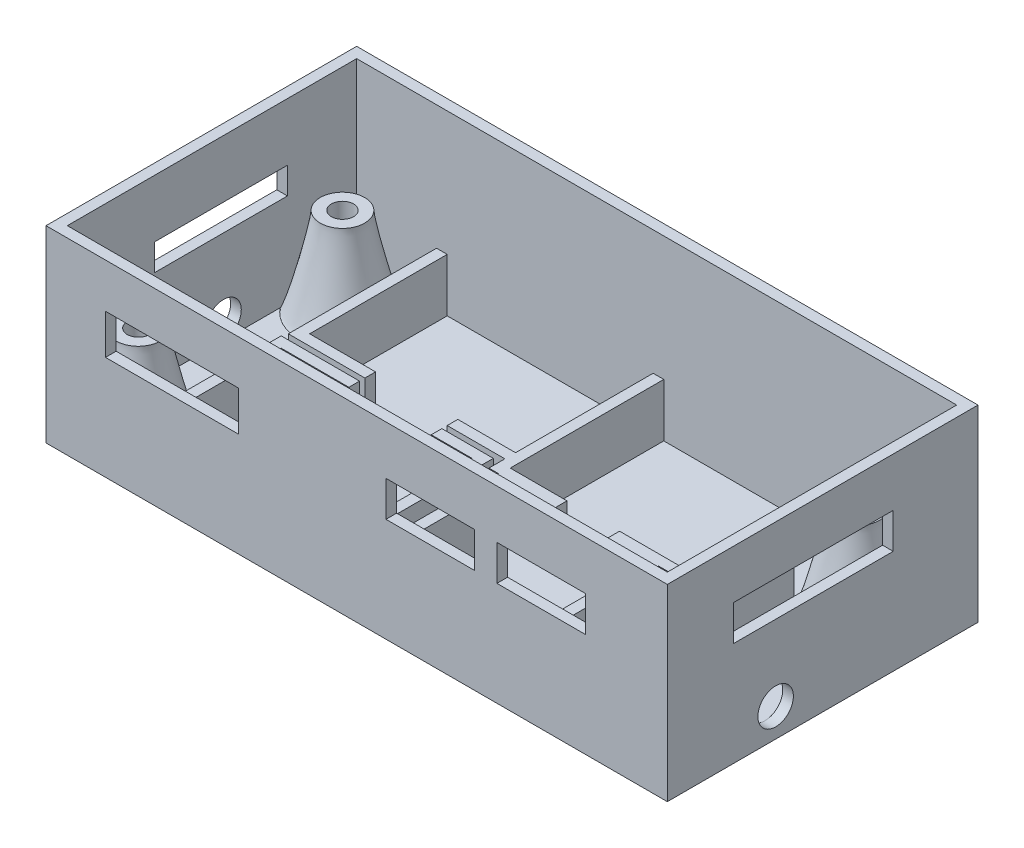
SolidWorks part; units mm, degrees
ref_plane "Front" through (0, 0, 0) normal (0, 0, 1) x (1, 0, 0)
ref_plane "Top" through (0, 0, 0) normal (0, 1, 0) x (1, 0, 0)
ref_plane "Right" through (0, 0, 0) normal (1, 0, 0) x (0, 0, -1)
sketch "Sketch1" plane through (0, 0, 0) normal (0, 1, 0) x (1, 0, 0)
  line L1 (0, 0) -> (70, 0)
  line L2 (0, 0) -> (0, -35)
  line L3 (0, -35) -> (70, -35)
  line L4 (70, 0) -> (70, -35)
  dimension "D1" = 35
  dimension "D2" = 70
extrude "Boss-Extrude1" add sketch "Sketch1" along normal blind 1.2
sketch "Sketch2" plane through (0, 1.2, 0) normal (0, 1, 0) x (1, 0, 0)
  line L0 (0, -35) -> (70, -35) construction
  line L1 (0, -35) -> (70, -35)
  line L2 (0, -35) -> (0, 0)
  line L3 (0, 0) -> (70, 0)
  line L4 (70, -35) -> (70, 0)
  line L5 (1.2, -33.8) -> (1.2, -1.2)
  line L6 (1.2, -1.2) -> (68.8, -1.2)
  line L7 (68.8, -33.8) -> (68.8, -1.2)
  line L8 (1.2, -33.8) -> (68.8, -33.8)
  dimension "D1" = 1.2
extrude "Boss-Extrude2" add sketch "Sketch2" along normal blind 20
sketch "Sketch3" plane through (0, 1.2, 0) normal (0, 1, 0) x (1, 0, 0)
  line L0 (1.2, -1.2) -> (1.2, -33.8) construction
  line L1 (1.2, -33.8) -> (68.8, -33.8) construction
  circle A0 centre (5.2, -29.8) radius 2.5
  circle A1 centre (63.2, -29.8) radius 2.5
  circle A2 centre (63.2, -6.8) radius 2.5
  circle A3 centre (5.2, -6.8) radius 2.5
  dimension "D1" = 5
  dimension "D4" = 2
  dimension "D2" = 4
  dimension "D3" = 4
  dimension "D5" = 2
extrude "Boss-Extrude3" add sketch "Sketch3" along normal blind 10
sketch "Sketch4" plane through (0, 11.2, 0) normal (0, 1, 0) x (1, 0, 0)
  circle A0 centre (5.2, -29.8) radius 1.25
  circle A1 centre (5.2, -6.8) radius 1.25
  circle A2 centre (63.2, -6.8) radius 1.25
  circle A3 centre (63.2, -29.8) radius 1.25
  dimension "D1" = 2.5
  dimension "D2" = 2.5
  dimension "D3" = 2.5
  dimension "D4" = 2.5
extrude "Cut-Extrude1" cut sketch "Sketch4" against normal through all
sketch "Sketch5" plane through (0, 0, 0) normal (-1, 0, 0) x (0, 0, 1)
  line L0 (0, 0) -> (35, 0) construction
  line L1 (9, 14.7) -> (24, 14.7)
  line L2 (9, 14.7) -> (9, 11.7)
  line L3 (9, 11.7) -> (24, 11.7)
  line L4 (24, 14.7) -> (24, 11.7)
  line L5 (35, 21.2) -> (35, 0) construction
  dimension "D1" = 3
  dimension "D2" = 15
  dimension "D3" = 11.7
  dimension "D4" = 11
extrude "Cut-Extrude2" cut sketch "Sketch5" against normal blind 2
sketch "Sketch7" plane through (0, 0, 33.8) normal (0, 0, -1) x (-1, 0, 0)
  line L0 (-68.8, 21.2) -> (-68.8, 1.2) construction
  line L1 (-50.8, 15.7) -> (-60.8, 15.7)
  line L2 (-50.8, 15.7) -> (-50.8, 11.7)
  line L3 (-50.8, 11.7) -> (-60.8, 11.7)
  line L4 (-60.8, 15.7) -> (-60.8, 11.7)
  line L5 (-38.3, 15.7) -> (-48.3, 15.7)
  line L6 (-38.3, 15.7) -> (-38.3, 11.7)
  line L7 (-38.3, 11.7) -> (-48.3, 11.7)
  line L8 (-48.3, 15.7) -> (-48.3, 11.7)
  line L9 (-1.2, 1.2) -> (-68.8, 1.2) construction
  dimension "D1" = 10
  dimension "D2" = 10
  dimension "D3" = 4
  dimension "D4" = 4
  dimension "D5" = 8
  dimension "D6" = 20.5
  dimension "D7" = 10.5
  dimension "D8" = 10.5
extrude "Cut-Extrude3" cut sketch "Sketch7" against normal blind 2
sketch "Sketch8" plane through (0, 0, 33.8) normal (0, 0, -1) x (-1, 0, 0)
  line L0 (-1.2, 1.2) -> (-68.8, 1.2) construction
  line L1 (-6.7, 16.2) -> (-21.7, 16.2)
  line L2 (-6.7, 16.2) -> (-6.7, 11.7)
  line L3 (-6.7, 11.7) -> (-21.7, 11.7)
  line L4 (-21.7, 16.2) -> (-21.7, 11.7)
  line L5 (-1.2, 21.2) -> (-1.2, 1.2) construction
  dimension "D1" = 15
  dimension "D2" = 4.5
  dimension "D3" = 10.5
  dimension "D4" = 5.5
extrude "Cut-Extrude4" cut sketch "Sketch8" against normal blind 2
sketch "Sketch9" plane through (68.8, 0, 0) normal (-1, 0, 0) x (0, 0, 1)
  line L0 (33.8, 1.2) -> (1.2, 1.2) construction
  line L1 (9.55, 15.7) -> (27.55, 15.7)
  line L2 (9.55, 15.7) -> (9.55, 11.7)
  line L3 (9.55, 11.7) -> (27.55, 11.7)
  line L4 (27.55, 15.7) -> (27.55, 11.7)
  line L5 (33.8, 21.2) -> (33.8, 1.2) construction
  dimension "D1" = 18
  dimension "D2" = 4
  dimension "D3" = 10.5
  dimension "D4" = 6.25
extrude "Cut-Extrude5" cut sketch "Sketch9" against normal blind 2
fillet "Fillet1" radius 2.5 4 edges at (63.2, 1.2, 32.3) (5.2, 1.2, 32.3) (63.2, 1.2, 9.3) (5.2, 1.2, 9.3) second distance 10 conic rho 0.1 first distance on face at (5.2, 1.2, 9.3)
sketch "Sketch10" plane through (0, 1.2, 0) normal (0, 1, 0) x (1, 0, 0)
  line L0 (68.8, -1.2) -> (1.2, -1.2) construction
  line L1 (11.4, -1.2) -> (34.6, -1.2)
  line L2 (11.4, -1.2) -> (11.4, -16.7)
  line L3 (11.4, -16.7) -> (34.6, -16.7)
  line L4 (34.6, -1.2) -> (34.6, -16.7)
  line L5 (10.2, -1.2) -> (10.2, -17.9)
  line L6 (10.2, -17.9) -> (35.8, -17.9)
  line L7 (35.8, -1.2) -> (35.8, -17.9)
  line L8 (10.2, 0) -> (35.8, 0)
  line L9 (11.4, -1.2) -> (10.2, -1.2)
  line L10 (34.6, -1.2) -> (35.8, -1.2)
  line L11 (1.2, -1.2) -> (1.2, -3.8004) construction
  line L12 (35.8, 0) -> (35.8, -17.9) construction
  line L13 (10.2, 0) -> (10.2, -17.9) construction
  dimension "D1" = 15.5
  dimension "D2" = 23.2
  dimension "D4" = 10.2
  dimension "D3" = 1.2
extrude "Boss-Extrude4" add sketch "Sketch10" along normal blind 6
sketch "Sketch11" plane through (0, 1.2, 0) normal (0, 1, 0) x (1, 0, 0)
  line L1 (57.9, -1.2) -> (59.1, -1.2)
  line L2 (35.8, -17.9) -> (35.8, -18.5)
  line L3 (35.8, -18.5) -> (57.9, -18.5)
  line L4 (57.9, -1.2) -> (57.9, -3.6462)
  line L5 (68.8, -1.2) -> (35.8, -1.2) construction
  line L6 (35.8, -19.7) -> (59.1, -19.7)
  line L7 (59.1, -1.2) -> (59.1, -3.6462)
  line L8 (35.8, -17.9) -> (34.6, -17.9)
  line L9 (10.2, -17.9) -> (35.8, -17.9) construction
  line L10 (59.1, -9.85) -> (57.9, -9.85)
  line L12 (59.1, -3.6462) -> (57.9, -3.6462)
  line L13 (57.9, -9.85) -> (57.9, -18.5)
  line L14 (59.1, -9.85) -> (59.1, -19.7)
  line L15 (57.9, -1.2) -> (57.9, -18.5) construction
  line L16 (34.6, -19.7) -> (59.1, -19.7) construction
  line L17 (59.1, 0) -> (59.1, -19.7) construction
  line L18 (34.6, 0) -> (34.6, -19.7) construction
  line L19 (34.6, 0) -> (59.1, 0) construction
  line L20 (35.8, -1.2) -> (57.9, -1.2) construction
  line L21 (34.6, -17.9) -> (34.6, -19.7)
  line L22 (34.6, -19.7) -> (35.8, -19.7)
  line L23 (35.8, -1.2) -> (35.8, -18.5) construction
  dimension "D1" = 17.3
  dimension "D2" = 22.1
  dimension "D4" = 1.2
  dimension "D3" = 1.2
extrude "Boss-Extrude5" add sketch "Sketch11" along normal blind 6
sketch "Sketch12" plane through (0, 1.2, 0) normal (0, 1, 0) x (1, 0, 0)
  line L0 (8.1996, -33.8) -> (60.2004, -33.8) construction
  line L2 (11.2, -33.8) -> (11.2, -19.7)
  line L3 (11.2, -19.7) -> (32.7, -19.7)
  line L4 (32.7, -33.8) -> (32.7, -19.7)
  line L5 (1.2, -9.7996) -> (1.2, -26.8004) construction
  line L6 (10, -33.8) -> (10, -18.5)
  line L7 (10, -18.5) -> (33.9, -18.5)
  line L8 (33.9, -33.8) -> (33.9, -18.5)
  line L9 (10, -35) -> (10, -18.5) construction
  line L10 (11.2, -33.8) -> (10, -33.8)
  line L11 (32.7, -33.8) -> (33.9, -33.8)
  line L12 (33.9, -35) -> (33.9, -18.5) construction
  line L13 (11.2, -33.8) -> (32.7, -33.8) construction
  line L14 (10, -35) -> (33.9, -35) construction
  dimension "D1" = 21.5
  dimension "D2" = 14.1
  dimension "D3" = 10
  dimension "D4" = 1.2
extrude "Boss-Extrude6" add sketch "Sketch12" along normal blind 6
sketch "Sketch13" plane through (0, 1.2, 0) normal (0, 1, 0) x (1, 0, 0)
  line L0 (33.9, -33.8) -> (60.2004, -33.8) construction
  line L2 (36.9, -33.8) -> (36.9, -20)
  line L3 (36.9, -20) -> (52.5, -20)
  line L4 (52.5, -33.8) -> (52.5, -20)
  line L5 (33.9, -33.8) -> (33.9, -18.5) construction
  line L6 (35.7, -33.8) -> (35.7, -19.7)
  line L8 (53.7, -33.8) -> (53.7, -19.7)
  line L10 (35.7, -33.8) -> (36.9, -33.8)
  line L11 (52.5, -33.8) -> (53.7, -33.8)
  line L12 (35.7, -19.7) -> (53.7, -19.7)
  line L13 (34.6, -19.7) -> (59.1, -19.7) construction
  line L14 (35.7, -35) -> (35.7, -18.8) construction
  line L15 (35.7, -18.8) -> (53.7, -18.8) construction
  line L16 (53.7, -35) -> (53.7, -18.8) construction
  line L17 (35.7, -35) -> (53.7, -35) construction
  line L18 (36.9, -33.8) -> (52.5, -33.8) construction
  dimension "D1" = 13.8
  dimension "D2" = 15.6
  dimension "D3" = 3
  dimension "D4" = 1.2
extrude "Boss-Extrude7" add sketch "Sketch13" along normal blind 6
sketch "Sketch14" plane through (0, 7.2, 0) normal (0, 1, 0) x (1, 0, 0)
  line L1 (18.8265, -21.5603) -> (28.0991, -21.5603)
  line L2 (18.8265, -21.5603) -> (18.8265, -15.13)
  line L3 (18.8265, -15.13) -> (28.0991, -15.13)
  line L4 (28.0991, -21.5603) -> (28.0991, -15.13)
  line L5 (42.1964, -21.5603) -> (48.1158, -21.5603)
  line L6 (42.1964, -21.5603) -> (42.1964, -16.7598)
  line L7 (42.1964, -16.7598) -> (48.1158, -16.7598)
  line L8 (48.1158, -21.5603) -> (48.1158, -16.7598)
extrude "Cut-Extrude6" cut sketch "Sketch14" against normal blind 5
sketch "Sketch15" plane through (1.2, 0, 0) normal (1, 0, 0) x (0, 0, -1)
  line L0 (-9.7996, 1.2) -> (-26.8004, 1.2) construction
  line L1 (-1.2, 21.2) -> (-1.2, 1.2) construction
  circle A0 centre (-16.2, 3.2) radius 2
  point P4 (0, 0)
  dimension "D1" = 4
  dimension "D2" = 2
  dimension "D3" = 15
extrude "Cut-Extrude7" cut sketch "Sketch15" against normal blind 2
sketch "Sketch16" plane through (68.8, 0, 0) normal (-1, 0, 0) x (0, 0, 1)
  line L0 (33.8, 1.2) -> (1.2, 1.2) construction
  line L1 (33.8, 21.2) -> (33.8, 1.2) construction
  circle A0 centre (22.8, 3.2) radius 2
  dimension "D1" = 4
  dimension "D2" = 2
  dimension "D3" = 11
extrude "Cut-Extrude8" cut sketch "Sketch16" against normal blind 2
